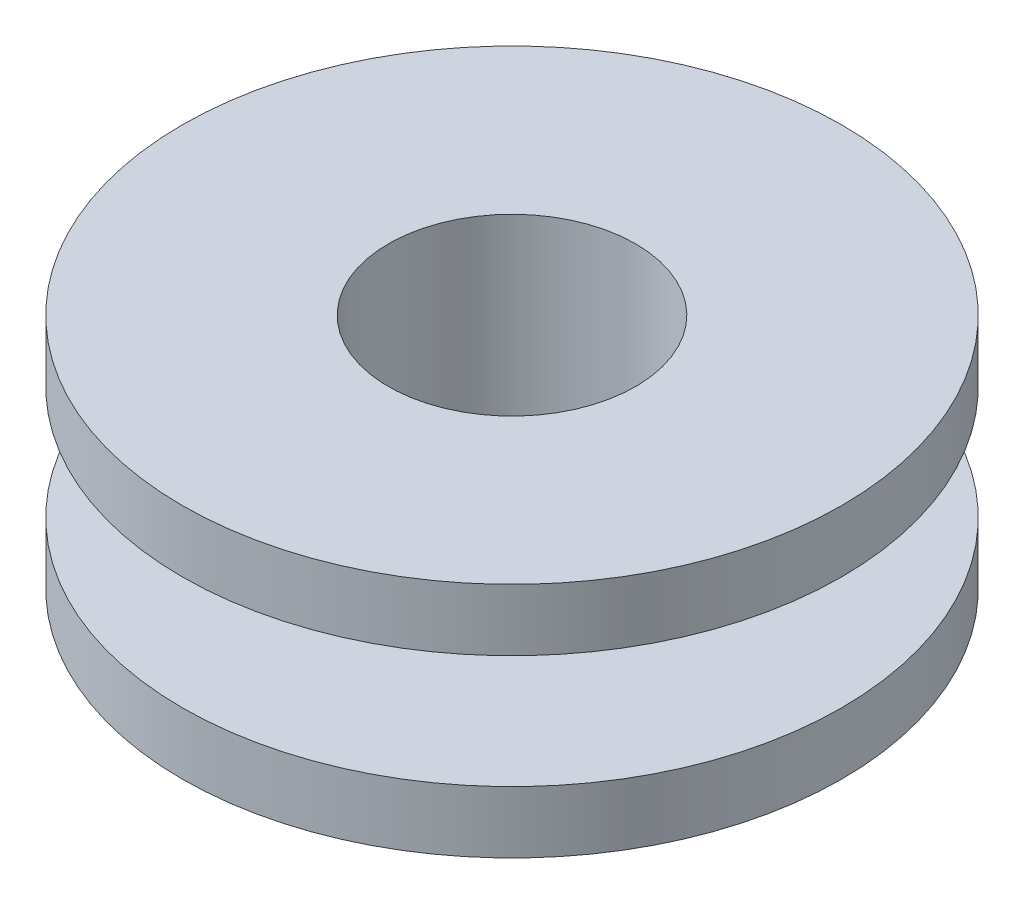
SolidWorks part; units mm, degrees
ref_plane "Front Plane" through (0, 0, 0) normal (0, 0, 1) x (1, 0, 0)
ref_plane "Top Plane" through (0, 0, 0) normal (0, 1, 0) x (1, 0, 0)
ref_plane "Right Plane" through (0, 0, 0) normal (1, 0, 0) x (0, 0, -1)
sketch "Sketch1" plane through (0, 0, 0) normal (0, 0, 1) x (1, 0, 0)
  line L0 (6, 0) -> (6, 11.5)
  line L1 (6, 11.5) -> (16, 11.5)
  line L2 (16, 11.5) -> (16, 8.5)
  line L3 (16, 8.5) -> (8, 8.5)
  line L4 (8, 8.5) -> (8, 3)
  line L5 (8, 3) -> (16, 3)
  line L6 (16, 3) -> (16, 0)
  line L7 (16, 0) -> (6, 0)
  line L8 (0, 0) -> (0, 17.7633) construction
  line L9 (0, 0) -> (-2.3464, 0) construction
  dimension "D1" = 8
  dimension "D2" = 16
  dimension "D3" = 11.5
  dimension "D4" = 3
  dimension "D5" = 3
  dimension "D6" = 2
revolve "Revolve1" add sketch "Sketch1" angle 360 about L8
